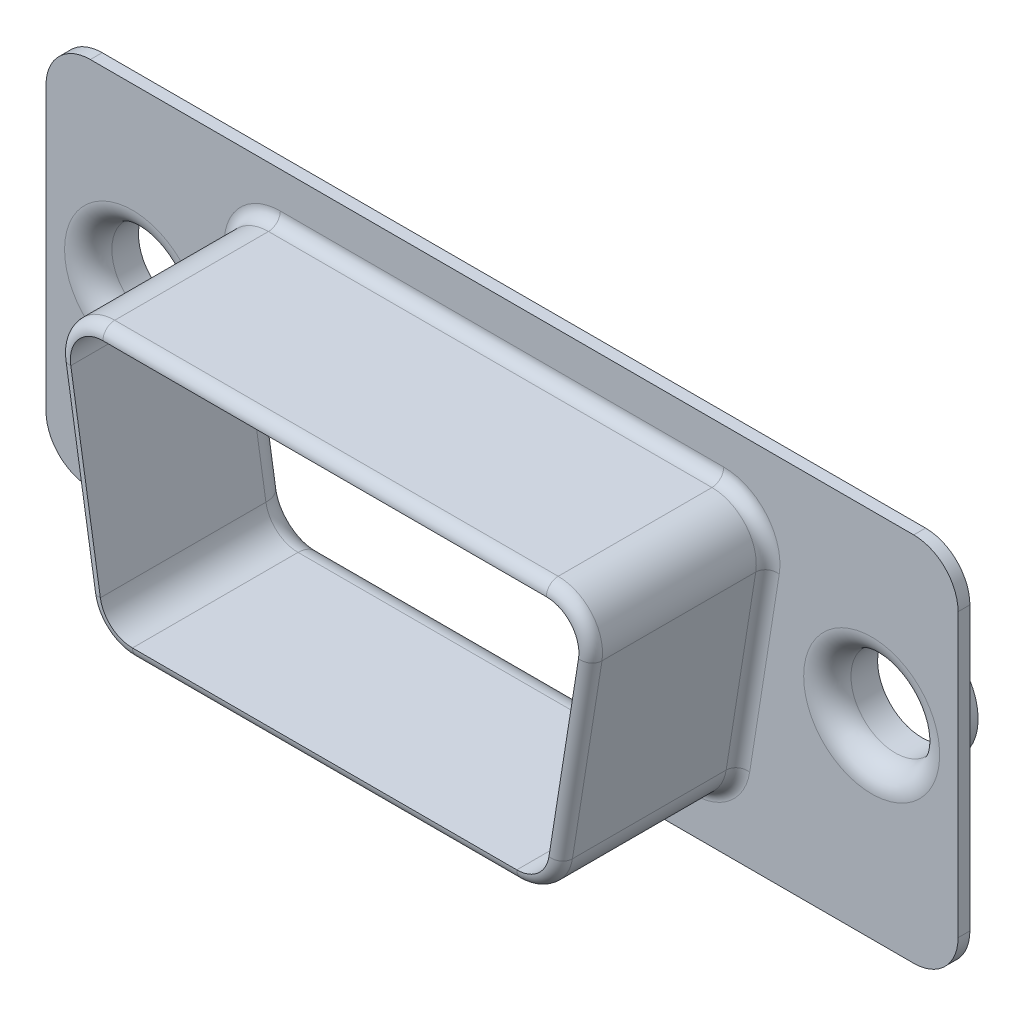
SolidWorks part; units mm, degrees
ref_plane "Front Plane" through (0, 0, 0) normal (0, 0, 1) x (1, 0, 0)
ref_plane "Top Plane" through (0, 0, 0) normal (0, 1, 0) x (1, 0, 0)
ref_plane "Right Plane" through (0, 0, 0) normal (1, 0, 0) x (0, 0, -1)
sketch "Sketch1" plane through (0, 0, 0) normal (0, 0, 1) x (1, 0, 0)
  line L1 (13.925, 6.275) -> (-13.925, 6.275)
  line L2 (15.425, 4.775) -> (15.425, -4.775)
  line L3 (13.925, -6.275) -> (-13.925, -6.275)
  line L4 (-15.425, 4.775) -> (-15.425, -4.775)
  line L5 (15.425, 6.275) -> (-15.425, -6.275) construction
  line L6 (15.425, -6.275) -> (-15.425, 6.275) construction
  arc A0 (15.425, -4.775) -> (13.925, -6.275) centre (13.925, -4.775) cw
  arc A1 (-13.925, -6.275) -> (-15.425, -4.775) centre (-13.925, -4.775) cw
  arc A2 (13.925, 6.275) -> (15.425, 4.775) centre (13.925, 4.775) cw
  arc A3 (-13.925, 6.275) -> (-15.425, 4.775) centre (-13.925, 4.775) ccw
  point P0 (0, 0)
  dimension "D3" = 1.5
  dimension "D1" = 30.85
  dimension "D2" = 12.55
base flange "Base-Flange1" sketch "Sketch1" thickness 0.4 reverse thickness direction no parameters "D1"=2.5
sketch "Sketch6" plane through (0, 0, 0) normal (0, 0, 1) x (1, 0, 0)
  line L0 (13.925, 6.275) -> (-13.925, 6.275) construction
  circle A0 centre (-12.497, 0.275) radius 1.5
  circle A1 centre (12.503, 0.275) radius 1.5
  dimension "D1" = 25
  dimension "D2" = 3
  dimension "D3" = 12.5
  dimension "D4" = 6
extrude "Cut-Extrude1" cut sketch "Sketch6" against normal blind 10 normal cut yes
sketch "Sketch7" plane through (0, 0, 0) normal (0, 0, 1) x (1, 0, 0)
  line L0 (-13.925, -6.275) -> (13.925, -6.275) construction
  line L1 (-15.425, 4.775) -> (-15.425, -4.775) construction
  line L2 (-8.9815, 2.9148) -> (-7.9815, -3.3852) construction
  line L3 (9, 4.65) -> (-9, 4.65) construction
  line L4 (-7.5, 4.65) -> (7.5, 4.65) construction
  line L5 (-6.5, -4.65) -> (6.5, -4.65) construction
  line L6 (-9, -4.65) -> (9, -4.65) construction
  line L7 (0, 4.65) -> (0, -4.65) construction
  line L8 (8.9815, 2.9148) -> (7.9815, -3.3852) construction
  line L9 (9, -4.65) -> (9, 4.65) construction
  line L10 (8.5864, 2.9776) -> (7.5864, -3.3224)
  line L11 (-6.5, -4.25) -> (6.5, -4.25)
  line L12 (-9, 4.65) -> (-9, -4.65) construction
  line L13 (-8.5864, 2.9776) -> (-7.5864, -3.3224)
  line L14 (-7.5, 4.25) -> (7.5, 4.25)
  arc A0 (-7.5, 4.65) -> (-8.9815, 2.9148) centre (-7.5, 3.15) ccw construction
  arc A1 (-7.9815, -3.3852) -> (-6.5, -4.65) centre (-6.5, -3.15) ccw construction
  arc A2 (7.9815, -3.3852) -> (6.5, -4.65) centre (6.5, -3.15) cw construction
  arc A3 (7.5, 4.65) -> (8.9815, 2.9148) centre (7.5, 3.15) cw construction
  arc A4 (7.5864, -3.3224) -> (6.5, -4.25) centre (6.5, -3.15) cw
  arc A5 (-7.5864, -3.3224) -> (-6.5, -4.25) centre (-6.5, -3.15) ccw
  arc A6 (-7.5, 4.25) -> (-8.5864, 2.9776) centre (-7.5, 3.15) ccw
  arc A7 (7.5, 4.25) -> (8.5864, 2.9776) centre (7.5, 3.15) cw
  point P8 (0, 4.65)
  point P9 (9, 0)
  point P23 (0, 4.65)
  dimension "D5" = 3
  dimension "D2" = 8
  dimension "D3" = 18
  dimension "D4" = 0.4
  dimension "D1" = 9.3
extrude "Cut-Extrude2" cut sketch "Sketch7" against normal blind 10 normal cut yes
sketch "Sketch8" plane through (0, 0, 0) normal (0, 0, 1) x (1, 0, 0)
  line L20 (7.5, 4.65) -> (-7.5, 4.65)
  line L21 (-8.9815, 2.9148) -> (-7.9815, -3.3852)
  line L22 (-6.5, -4.65) -> (6.5, -4.65)
  line L23 (7.9815, -3.3852) -> (8.9815, 2.9148)
  line L24 (7.5864, -3.3224) -> (8.5864, 2.9776)
  line L25 (-6.5, -4.25) -> (6.5, -4.25)
  line L26 (-8.5864, 2.9776) -> (-7.5864, -3.3224)
  line L27 (7.5, 4.25) -> (-7.5, 4.25)
  line L28 (7.5864, -3.3224) -> (8.5864, 2.9776)
  line L29 (-6.5, -4.25) -> (6.5, -4.25)
  line L30 (-8.5864, 2.9776) -> (-7.5864, -3.3224)
  line L31 (7.5, 4.25) -> (-7.5, 4.25)
  arc A16 (-7.5, 4.65) -> (-8.9815, 2.9148) centre (-7.5, 3.15) ccw
  arc A17 (-7.9815, -3.3852) -> (-6.5, -4.65) centre (-6.5, -3.15) ccw
  arc A18 (6.5, -4.65) -> (7.9815, -3.3852) centre (6.5, -3.15) ccw
  arc A19 (8.9815, 2.9148) -> (7.5, 4.65) centre (7.5, 3.15) ccw
  arc A20 (8.5864, 2.9776) -> (7.5, 4.25) centre (7.5, 3.15) ccw
  arc A21 (6.5, -4.25) -> (7.5864, -3.3224) centre (6.5, -3.15) ccw
  arc A22 (-7.5864, -3.3224) -> (-6.5, -4.25) centre (-6.5, -3.15) ccw
  arc A23 (-7.5, 4.25) -> (-8.5864, 2.9776) centre (-7.5, 3.15) ccw
  arc A24 (8.5864, 2.9776) -> (7.5, 4.25) centre (7.5, 3.15) ccw
  arc A25 (6.5, -4.25) -> (7.5864, -3.3224) centre (6.5, -3.15) ccw
  arc A26 (-7.5864, -3.3224) -> (-6.5, -4.25) centre (-6.5, -3.15) ccw
  arc A27 (-7.5, 4.25) -> (-8.5864, 2.9776) centre (-7.5, 3.15) ccw
  dimension "D1" = 0
  dimension "D2" = 0.4
extrude "Boss-Extrude1" add sketch "Sketch8" along normal blind 6
fillet "Fillet1" radius 0.4 8 edges at (7.474, -4.2908, 0) (0, -4.65, 0) (-7.474, -4.2908, 0) (-8.4815, -0.2352, 0) (-8.6408, 4.124, 0) (0, 4.65, 0) (8.6408, 4.124, 0) (8.4815, -0.2352, 0)
fillet "Fillet2" radius 0.8 8 edges at (-8.3366, 3.8643, -0.4) (-8.0864, -0.1724, -0.4) (-7.2143, -3.9866, -0.4) (0, -4.25, -0.4) (7.2143, -3.9866, -0.4) (8.0864, -0.1724, -0.4) (8.3366, 3.8643, -0.4) (0, 4.25, -0.4)
sketch "Sketch10" plane through (0, 0, -0.4) normal (0, 0, -1) x (-1, 0, 0)
  circle A2 centre (-12.503, 0.275) radius 1.5
  circle A3 centre (-12.503, 0.275) radius 1.5
  circle A4 centre (-12.503, 0.275) radius 1.9
  circle A5 centre (12.497, 0.275) radius 1.5
  circle A6 centre (12.497, 0.275) radius 1.5
  circle A7 centre (12.497, 0.275) radius 1.9
  dimension "D1" = 0
  dimension "D2" = 0
  dimension "D3" = 0.4
extrude "Boss-Extrude2" add sketch "Sketch10" along normal blind 1.3
fillet "Fillet3" radius 0.4 2 edges at (10.603, 0.275, -0.4) (-14.397, 0.275, -0.4)
fillet "Fillet4" radius 0.8 2 edges at (-10.997, 0.275, 0) (14.003, 0.275, 0)
fillet "Fillet5" radius 0.4 8 edges at (8.6408, 4.124, 6) (8.4815, -0.2352, 6) (7.474, -4.2908, 6) (0, -4.65, 6) (-7.474, -4.2908, 6) (-8.4815, -0.2352, 6) (-8.6408, 4.124, 6) (0, 4.65, 6)
sketch "Bend-Lines1" [suppressed] plane through (0, 0, 0) normal (0, 1, 0) x (1, 0, 0)
sketch "Bounding-Box1" [suppressed] plane through (0, 0, 0) normal (0, 1, 0) x (1, 0, 0)
sheet metal parameters "Sheet-Metal1" thickness 0.4 parameters "D1"=2.5
flat pattern "Flat-Pattern1" [suppressed]
sketch "Bend-Lines2" plane through (0, 0, 0) normal (0, 1, 0) x (1, 0, 0)
sketch3d "Bounding-Box2" [suppressed]
  line L0 (29.35, -1.5, 0) -> (-1.5, -1.5, 0) construction
  line L1 (29.35, 11.05, 0) -> (-1.5, 11.05, 0) construction
  line L2 (29.35, -1.5, 0) -> (29.35, 11.05, 0) construction
  line L3 (-1.5, -1.5, 0) -> (-1.5, 11.05, 0) construction
sheet metal parameters "Sheet-Metal2" thickness 0.4 parameters "D1"=2.5
flat pattern "Flat-Pattern1"
sketch "Bend-Lines2" plane through (0, 0, 0) normal (0, 1, 0) x (1, 0, 0)
sketch3d "Bounding-Box2" [suppressed]
  line L0 (-29.35, -1.5, 0) -> (1.5, -1.5, 0) construction
  line L1 (-29.35, 11.05, 0) -> (1.5, 11.05, 0) construction
  line L2 (-29.35, -1.5, 0) -> (-29.35, 11.05, 0) construction
  line L3 (1.5, -1.5, 0) -> (1.5, 11.05, 0) construction
sheet metal parameters "Sheet-Metal3" thickness 0.4 parameters "D1"=2.5
flat pattern "Flat-Pattern1"
sketch "Bend-Lines2" plane through (0, 0, 0) normal (0, 1, 0) x (1, 0, 0)
sketch3d "Bounding-Box2" [suppressed]
  line L0 (-29.35, -1.5, 0) -> (1.5, -1.5, 0) construction
  line L1 (-29.35, 11.05, 0) -> (1.5, 11.05, 0) construction
  line L2 (-29.35, -1.5, 0) -> (-29.35, 11.05, 0) construction
  line L3 (1.5, -1.5, 0) -> (1.5, 11.05, 0) construction
sheet metal parameters "Sheet-Metal4" thickness 0.4 parameters "D1"=2.5
flat pattern "Flat-Pattern1"
sketch "Bend-Lines2" plane through (0, 0, 0) normal (0, 1, 0) x (1, 0, 0)
sketch3d "Bounding-Box2" [suppressed]
  line L0 (-29.35, -1.5, 0) -> (1.5, -1.5, 0) construction
  line L1 (-29.35, 11.05, 0) -> (1.5, 11.05, 0) construction
  line L2 (-29.35, -1.5, 0) -> (-29.35, 11.05, 0) construction
  line L3 (1.5, -1.5, 0) -> (1.5, 11.05, 0) construction
sheet metal parameters "Sheet-Metal5" thickness 0.4 parameters "D1"=2.5
flat pattern "Flat-Pattern1"
sketch "Bend-Lines2" plane through (0, 0, 0) normal (0, 1, 0) x (1, 0, 0)
sketch3d "Bounding-Box2" [suppressed]
  line L0 (-29.35, -1.5, 0) -> (1.5, -1.5, 0) construction
  line L1 (-29.35, 11.05, 0) -> (1.5, 11.05, 0) construction
  line L2 (-29.35, -1.5, 0) -> (-29.35, 11.05, 0) construction
  line L3 (1.5, -1.5, 0) -> (1.5, 11.05, 0) construction
